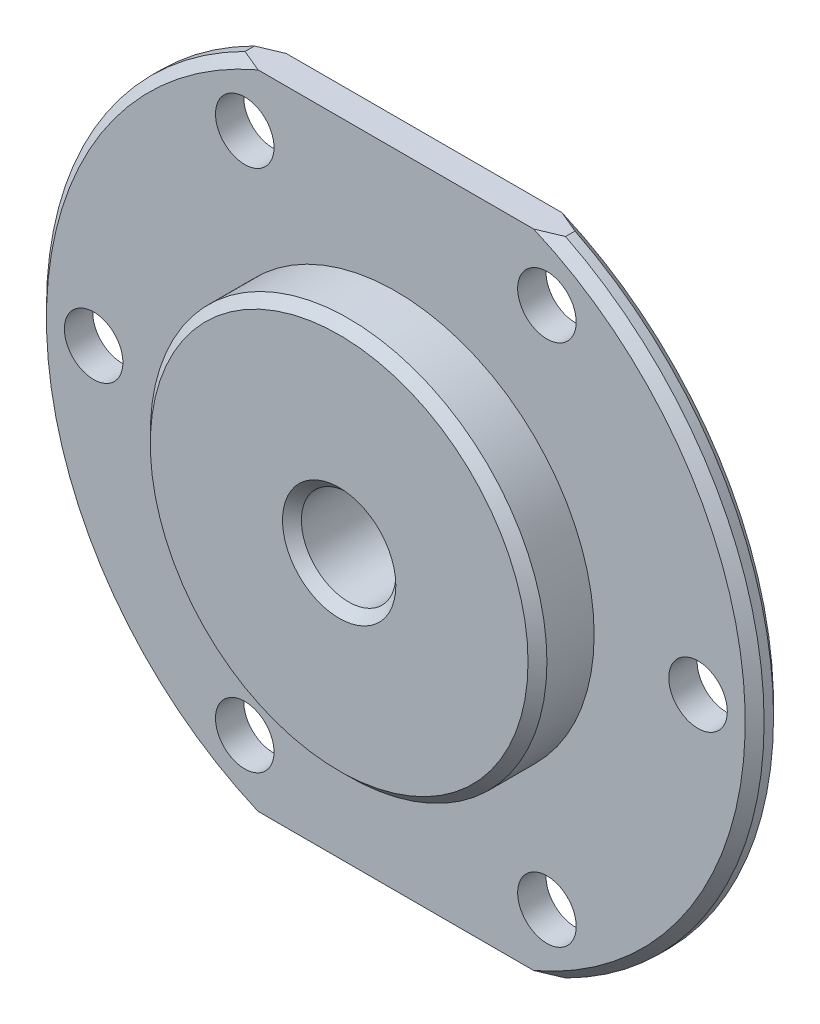
SolidWorks part; units mm, degrees
ref_plane "Front Plane" through (0, 0, 0) normal (0, 0, 1) x (1, 0, 0)
ref_plane "Top Plane" through (0, 0, 0) normal (0, 1, 0) x (1, 0, 0)
ref_plane "Right Plane" through (0, 0, 0) normal (1, 0, 0) x (0, 0, -1)
sketch "Sketch1" plane through (0, 0, 0) normal (0, 0, 1) x (1, 0, 0)
  line L0 (0, 0) -> (0, -13388.832) construction
  line L1 (0, 0) -> (13388.832, 0) construction
  line L2 (-8.485, 17) -> (8.485, 17)
  line L3 (-8.485, -17) -> (8.485, -17)
  arc A0 (-8.485, 17) -> (-8.485, -17) centre (0, 0) ccw
  arc A1 (8.485, -17) -> (8.485, 17) centre (0, 0) ccw
  point P11 (0, 0)
  point P12 (0, 0)
  point P13 (0, 0)
  dimension "D1" = 16.97
  dimension "D2" = 16.97
  dimension "D3" = 34
extrude "Boss-Extrude1" add sketch "Sketch1" along normal blind 1.5
sketch "Sketch3" plane through (0, 0, 1.5) normal (0, 0, 1) x (1, 0, 0)
  circle A0 centre (0, 0) radius 10.5
  dimension "D1" = 21
extrude "Boss-Extrude2" add sketch "Sketch3" along normal blind 3
sketch "Sketch4" plane through (0, 0, 4.5) normal (0, 0, 1) x (1, 0, 0)
  circle A0 centre (0, 0) radius 2.5
  dimension "D1" = 5
extrude "Cut-Extrude1" cut sketch "Sketch4" against normal blind 10
sketch "Sketch5" plane through (0, 0, 0) normal (0, 0, -1) x (-1, 0, 0)
  circle A0 centre (0, 0) radius 5
  circle M1 centre (0, 0) radius 2.5
  dimension "D1" = 10
extrude "Boss-Extrude3" add sketch "Sketch5" along normal blind 5 contours A0 M1 region at (4.8586, 0, 0)
sketch "Sketch6" plane through (0, 0, 1.5) normal (0, 0, 1) x (1, 0, 0)
  line L0 (0, 0) -> (0, -50000) construction
  line L1 (0, 0) -> (50000, 0) construction
  circle A0 centre (0, 0) radius 16 construction
  circle A1 centre (-16, 0) radius 1.55
  circle A2 centre (-8, 13.8564) radius 1.55
  circle A3 centre (8, 13.8564) radius 1.55
  circle A4 centre (16, 0) radius 1.55
  circle A5 centre (8, -13.8564) radius 1.55
  circle A6 centre (-8, -13.8564) radius 1.55
  point P22 (0, 0)
  dimension "D1" = 32
  dimension "D2" = 3.1
  dimension "D3" = 6
extrude "Cut-Extrude2" cut sketch "Sketch6" against normal blind 5
chamfer "Chamfer1" distance 0.5 angle 45 6 edges at (18.9999, 0, 0) (-18.9999, 0, 0) (18.9999, 0, 1.5) (-18.9999, 0, 1.5) (10.5, 0, 4.5) (2.5, 0, 4.5)
chamfer "Chamfer2" distance 0.5 angle 45 2 edges at (-2.5, 0, -5) (-5, 0, -5)
